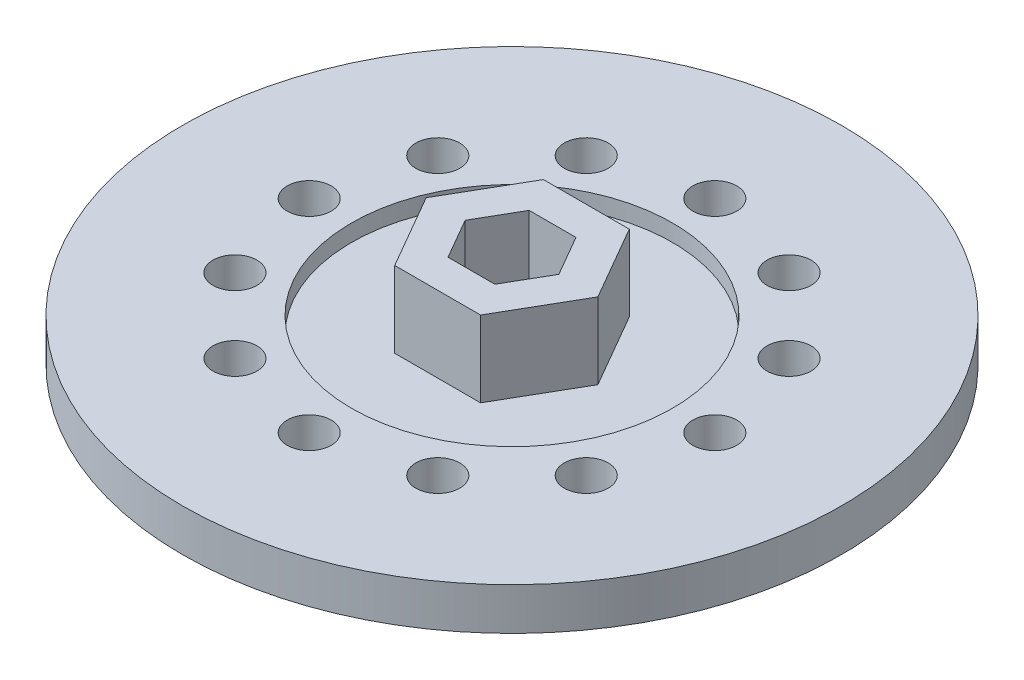
SolidWorks part; units mm, degrees
ref_plane "Front Plane" through (0, 0, 0) normal (0, 0, 1) x (1, 0, 0)
ref_plane "Top Plane" through (0, 0, 0) normal (0, 1, 0) x (1, 0, 0)
ref_plane "Right Plane" through (0, 0, 0) normal (1, 0, 0) x (0, 0, -1)
sketch "Sketch1" plane through (0, 0, 0) normal (0, 1, 0) x (1, 0, 0)
  circle A0 centre (0, 0) radius 49.53
  dimension "D1" = 99.06
extrude "Boss-Extrude1" add sketch "Sketch1" along normal blind 15.24
sketch "Sketch4" plane through (0, 15.24, 0) normal (0, 1, 0) x (1, 0, 0)
  line L0 (-3.5195, 6.096) -> (3.5195, 6.096)
  line L1 (3.5195, 6.096) -> (7.0391, 0)
  line L2 (7.0391, 0) -> (3.5195, -6.096)
  line L3 (3.5195, -6.096) -> (-3.5195, -6.096)
  line L4 (-3.5195, -6.096) -> (-7.0391, 0)
  line L5 (-7.0391, 0) -> (-3.5195, 6.096)
  point P7 (0, 6.096)
  dimension "D1" = 120
  dimension "D2" = 12.192
extrude "Hex hole" cut sketch "Sketch4" against normal blind 13.97 contours L5 L0 L1 L2 L3 L4
sketch "Sketch5" plane through (0, 1.27, 0) normal (0, 1, 0) x (1, 0, 0)
  circle A0 centre (0, 0) radius 4.191
  dimension "D1" = 8.382
extrude "Centerhole" cut sketch "Sketch5" against normal through all contours A0
sketch "Sketch6" plane through (0, 15.24, 0) normal (0, 1, 0) x (1, 0, 0)
  line L27 (12.9049, 0) -> (6.4525, 11.176)
  line L28 (6.4525, -11.176) -> (12.9049, 0)
  line L29 (-6.4525, -11.176) -> (6.4525, -11.176)
  line L30 (-12.9049, 0) -> (-6.4525, -11.176)
  line L31 (-6.4525, 11.176) -> (-12.9049, 0)
  line L32 (6.4525, 11.176) -> (-6.4525, 11.176)
  line L33 (12.9049, 0) -> (6.4525, 11.176)
  line L34 (6.4525, -11.176) -> (12.9049, 0)
  line L35 (-6.4525, -11.176) -> (6.4525, -11.176)
  line L36 (-12.9049, 0) -> (-6.4525, -11.176)
  line L37 (-6.4525, 11.176) -> (-12.9049, 0)
  line L38 (6.4525, 11.176) -> (-6.4525, 11.176)
  circle A2 centre (0, 0) radius 39.37
  circle A3 centre (0, 0) radius 39.37
  dimension "D1" = 10.16
  dimension "D2" = 5.08
extrude "Cut-Extrude1" cut sketch "Sketch6" against normal offset from surface (11.43 mm away) 3.81 up to face at (0, 0, 4.191)
sketch "Sketch7" plane through (0, 0, 0) normal (0, -1, 0) x (1, 0, 0)
  circle A0 centre (0, 30.48) radius 3.302
  circle A1 centre (15.24, 26.3965) radius 3.302
  circle A2 centre (26.3965, 15.24) radius 3.302
  circle A3 centre (30.48, 0) radius 3.302
  circle A4 centre (26.3965, -15.24) radius 3.302
  circle A5 centre (15.24, -26.3965) radius 3.302
  circle A6 centre (0, -30.48) radius 3.302
  circle A7 centre (-15.24, -26.3965) radius 3.302
  circle A8 centre (-26.3965, -15.24) radius 3.302
  circle A9 centre (-30.48, 0) radius 3.302
  circle A10 centre (-26.3965, 15.24) radius 3.302
  circle A11 centre (-15.24, 26.3965) radius 3.302
  point P27 (0, 0)
  dimension "D1" = 6.604
  dimension "D2" = 30.48
extrude "Cut-Extrude2" cut sketch "Sketch7" against normal through all
sketch "Sketch8" plane through (0, 15.24, 0) normal (0, 1, 0) x (1, 0, 0)
  circle A0 centre (0, 0) radius 39.37
  circle A1 centre (0, 0) radius 49.53
extrude "Cut-Extrude3" cut sketch "Sketch8" against normal up to surface (11.43 mm away) up to face at (-26.3965, 3.81, -11.938)
sketch "Sketch9" plane through (0, 3.81, 0) normal (0, 1, 0) x (1, 0, 0)
  circle A0 centre (0, 0) radius 24.13
  circle A1 centre (0, 0) radius 49.53
  circle A2 centre (0, 0) radius 49.53 construction
  circle A3 centre (0, 30.48) radius 3.302
  circle A4 centre (0, 30.48) radius 3.302 construction
  circle A5 centre (15.24, 26.3965) radius 3.302
  circle A6 centre (26.3965, 15.24) radius 3.302
  circle A7 centre (30.48, 0) radius 3.302
  circle A8 centre (26.3965, -15.24) radius 3.302
  circle A9 centre (15.24, -26.3965) radius 3.302
  circle A10 centre (0, -30.48) radius 3.302
  circle A11 centre (-15.24, -26.3965) radius 3.302
  circle A12 centre (-26.3965, -15.24) radius 3.302
  circle A13 centre (-30.48, 0) radius 3.302
  circle A14 centre (-26.3965, 15.24) radius 3.302
  circle A15 centre (-15.24, 26.3965) radius 3.302
  point P11 (0, 0)
  point P12 (-26.3965, 15.24)
  point P36 (0, 0)
  dimension "D1" = 25.4
  dimension "D2" = 12
extrude "Boss-Extrude2" add sketch "Sketch9" along normal blind 2.54
